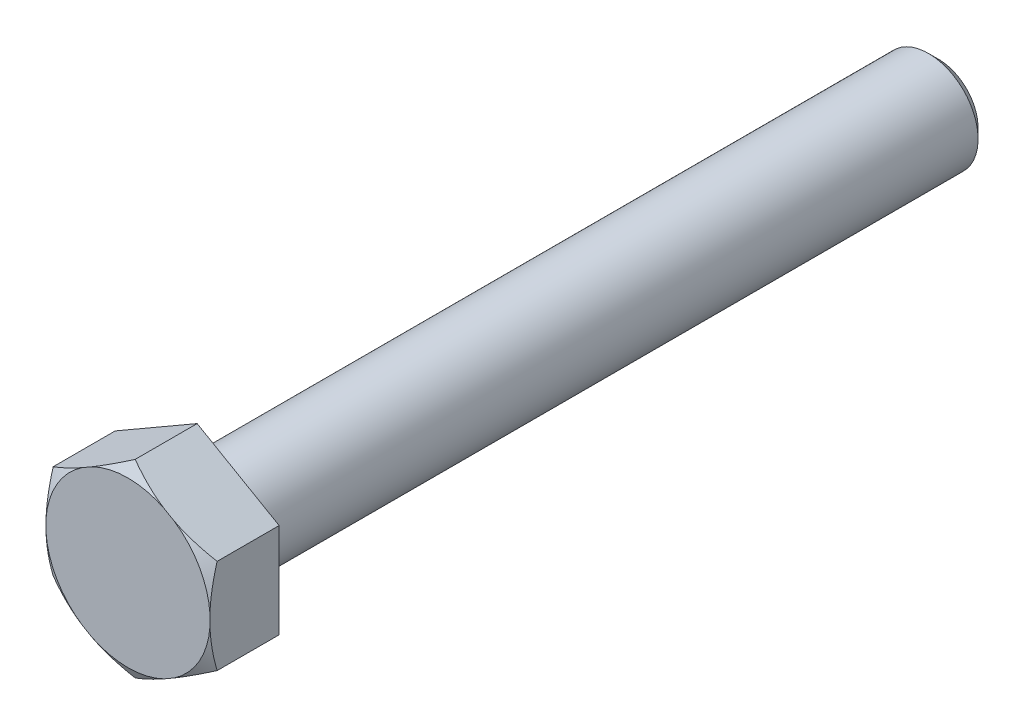
SolidWorks part; units mm, degrees
material "Простая углеродистая сталь"
ref_plane "Спереди" through (0, 0, 0) normal (0, 0, 1) x (1, 0, 0)
ref_plane "Сверху" through (0, 0, 0) normal (0, 1, 0) x (1, 0, 0)
ref_plane "Справа" through (0, 0, 0) normal (1, 0, 0) x (0, 0, -1)
sketch "Эскиз1" plane through (0, 0, 0) normal (0, 1, 0) x (1, 0, 0)
  line L0 (0, 0) -> (-4, 0)
  line L1 (-4, 0) -> (-4, 2.8)
  line L2 (-4, 2.8) -> (-2, 2.8)
  line L3 (-2, 2.8) -> (-2, 32.8)
  line L4 (-2, 32.8) -> (0, 32.8)
  line L5 (0, 32.8) -> (0, 0)
  dimension "D1" = 4
  dimension "D2" = 2.8
  dimension "D3" = 30
  dimension "D4" = 2
revolve "Повернуть1" add sketch "Эскиз1" angle 360 about L5
sketch "Эскиз2" plane through (0, 0, 0) normal (0, 0, 1) x (1, 0, 0)
  line L1 (0, 3.83) -> (-3.3169, 1.915)
  line L2 (-3.3169, 1.915) -> (-3.3169, -1.915)
  line L3 (-3.3169, -1.915) -> (0, -3.83)
  line L4 (0, -3.83) -> (3.3169, -1.915)
  line L5 (3.3169, -1.915) -> (3.3169, 1.915)
  line L6 (3.3169, 1.915) -> (0, 3.83)
  circle A0 centre (0, 0) radius 3.3169 construction
  dimension "D1" = 7.66
extrude "Вырез-Вытянуть1" cut sketch "Эскиз2" against normal up to surface (2.8 mm away) flip side to cut up to face at (-4, 0, -2.8)
sketch "Эскиз3" plane through (0, 0, 0) normal (1, 0, 0) x (0, 0, -1)
  line L1 (0, 0) -> (-50000, 0) construction
  line L3 (0, 3.83) -> (0.2916, 3.83)
  line L5 (2.8, 3.83) -> (0, 3.83) construction
  line L12 (0.2916, 3.83) -> (0, 3.325)
  line L13 (0, 1.915) -> (0, 3.83) construction
  line L14 (0, 3.325) -> (0, 3.83)
  dimension "D1" = 30
  dimension "D2" = 3.325
revolve "Вырез-Повернуть1" cut sketch "Эскиз3" angle 360 about L1
chamfer "Фаска1" distance 0.4 angle 45 1 edges at (-2, 0, -32.8)
fillet "Скругление1" radius 0.4 1 edges at (-2, 0, -2.8)
